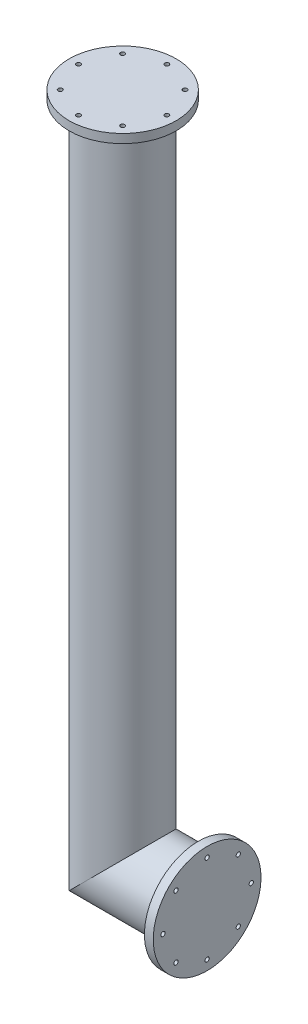
SolidWorks part; units mm, degrees
other "Elemento de detalle1"
other "Carpeta de soldadura"
other "Cordón de soldadura1"
material "6063-T5"
ref_plane "Front" through (0, 0, 0) normal (0, 0, 1) x (1, 0, 0)
ref_plane "Top" through (0, 0, 0) normal (0, 1, 0) x (1, 0, 0)
ref_plane "Right" through (0, 0, 0) normal (1, 0, 0) x (0, 0, -1)
sketch "Croquis1" plane through (0, 0, 0) normal (1, 0, 0) x (0, 0, -1)
  circle A0 centre (0, 0) radius 42.75
  dimension "D1" = 85.5
extrude "Saliente-Extruir1" add sketch "Croquis1" along normal mid plane 7
sketch "Croquis2" plane through (0, 0, 0) normal (0, 0, 1) x (1, 0, 0)
  line L0 (-13.5, -50) -> (-63.5, 0) construction
  line L2 (3.85, 0) -> (-3.85, 0) construction
  line L4 (-3.5, 42.75) -> (-3.5, -42.75) construction
  dimension "D1" = 45
  dimension "D2" = 10
  dimension "D3" = 50
ref_plane "Plano1" through (-63.5, 0, 0) normal (-0.7071, 0.7071, 0) x (0, 0, 1)
sketch "Croquis3" plane through (-3.5, 0, 0) normal (-1, 0, 0) x (0, 0, 1)
  circle A0 centre (0, 0) radius 30
  circle A1 centre (0, 0) radius 25
  dimension "D1" = 60
  dimension "D2" = 50
extrude "Saliente-Extruir2" add sketch "Croquis3" along normal up to surface (60 mm away) up to plane "Plano1"
ref_plane "Plano2" through (0, 522, 0) normal (0, 1, 0) x (1, 0, 0)
sketch "Croquis4" plane through (0, 522, 0) normal (0, 1, 0) x (1, 0, 0)
  circle A0 centre (-63.5, 0) radius 30 construction
  circle A1 centre (-63.5, 0) radius 30
  circle A2 centre (-63.5, 0) radius 25 construction
  circle A3 centre (-63.5, 0) radius 25
extrude "Saliente-Extruir3" add sketch "Croquis4" against normal up to surface (522 mm away) separate body up to face at (-38.5, 25, 0)
hole_wizard "Refrentado para tornillo con cabeza troncocónica de M31" positions "Croquis5" profile "Croquis7" counterbore size "M3" standard "Ansi Metric" end condition up to next
sketch "Croquis5" plane through (-3.5, 0, 0) normal (-1, 0, 0) x (0, 0, 1)
  line L0 (0, -60.225) -> (0, 60.225) construction
  line L1 (47.025, 0) -> (-47.025, 0) construction
  point P0 (0, 35)
  point P12 (24.7487, 24.7487)
  point P13 (35, 0)
  point P14 (24.7487, -24.7487)
  point P15 (0, -35)
  point P16 (-24.7487, -24.7487)
  point P17 (-35, 0)
  point P18 (-24.7487, 24.7487)
  dimension "D1" = 35
  dimension "D2" = 8
sketch "Croquis7" plane through (-3.5, 35, 0) normal (0, 1, 0) x (0, 0, 1)
  line L0 (0, 0) -> (0, 7)
  line L1 (0, 7) -> (1.7, 7)
  line L3 (1.7, 7) -> (1.7, 2.4)
  line L4 (1.7, 2.4) -> (3.5, 2.4)
  line L5 (3.5, 2.4) -> (3.5, 0)
  line L7 (3.5, 0) -> (0, 0)
  line L11 (0, -6.35) -> (0, 107.95) construction
  dimension "Diámetro de taladro hasta el siguiente" = 3.4
  dimension "Profundidad de taladro hasta el siguiente" = 7
  dimension "Diámetro de refrentado" = 7
  dimension "Profundidad de refrentado" = 2.4
sketch "Croquis8" plane through (0, 522, 0) normal (0, 1, 0) x (1, 0, 0)
  line L0 (-60.225, 0) -> (60.225, 0) construction
  circle A0 centre (-63.5, 0) radius 42.5
  circle A1 centre (-63.5, 0) radius 25 construction
  dimension "D1" = 85
extrude "Saliente-Extruir4" add sketch "Croquis8" along normal blind 7
hole_wizard "Refrentado para tornillo con cabeza troncocónica de M32" positions "Croquis9" profile "Croquis10" counterbore size "M3" standard "Ansi Metric" end condition up to next
sketch "Croquis9" plane through (0, 522, 0) normal (0, -1, 0) x (-1, 0, 0)
  line L0 (63.5, 0) -> (63.5, -35) construction
  line L1 (-60.225, 0) -> (60.225, 0) construction
  line L4 (63.5, 0) -> (63.5, 35) construction
  circle A0 centre (63.5, 0) radius 30 construction
  point P0 (63.5, -35)
  point P24 (38.7513, -24.7487)
  point P25 (28.5, 0)
  point P26 (38.7513, 24.7487)
  point P27 (63.5, 35)
  point P28 (88.2487, 24.7487)
  point P29 (98.5, 0)
  point P30 (88.2487, -24.7487)
  dimension "D1" = 35
  dimension "D3" = 8
sketch "Croquis10" plane through (-63.5, 522, 35) normal (1, 0, 0) x (0, 0, -1)
  line L0 (0, 0) -> (0, 7.001)
  line L1 (0, 7.001) -> (1.7, 7.001)
  line L3 (1.7, 7.001) -> (1.7, 2.4)
  line L4 (1.7, 2.4) -> (3.5, 2.4)
  line L5 (3.5, 2.4) -> (3.5, 0)
  line L7 (3.5, 0) -> (0, 0)
  line L11 (0, -6.35) -> (0, 107.95) construction
  dimension "Diámetro de taladro hasta el siguiente" = 3.4
  dimension "Profundidad de taladro hasta el siguiente" = 7.001
  dimension "Diámetro de refrentado" = 7
  dimension "Profundidad de refrentado" = 2.4
